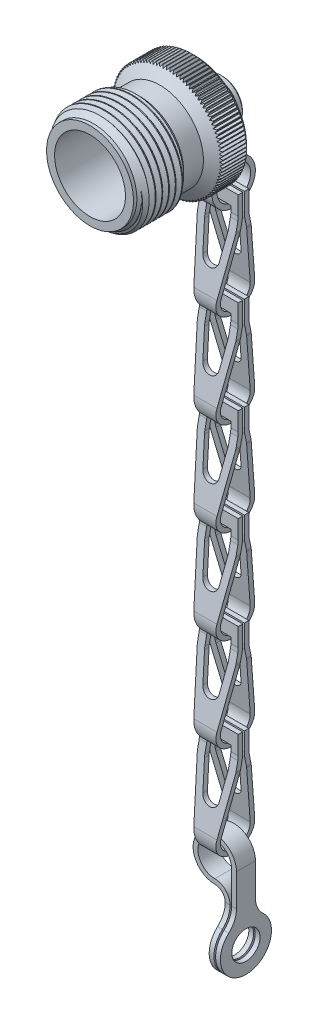
SolidWorks part; units mm, degrees
ref_plane "Front Plane" through (0, 0, 0) normal (0, 0, 1) x (1, 0, 0)
ref_plane "Top Plane" through (0, 0, 0) normal (0, 1, 0) x (1, 0, 0)
ref_plane "Right Plane" through (0, 0, 0) normal (1, 0, 0) x (0, 0, -1)
sketch "Sketch1" plane through (0, 0, 0) normal (1, 0, 0) x (0, 0, -1)
  line L0 (16.6624, 8.7249) -> (16.6624, -8.7249) construction
  line L2 (16.6624, 0) -> (16.6624, -114.3) construction
  line L4 (0, 7.9375) -> (0, -7.9375) construction
  line L5 (0, 7.9375) -> (1.0583, 7.9375) construction
  line L13 (0, 0) -> (16.6624, 0) construction
  circle A0 centre (16.6624, -114.3) radius 2.1082 construction
  point P14 (16.6624, -57.15)
  dimension "D" = 4.2164
  dimension "A Thread" = 15.875
  dimension "A Pitch" = 1.0583
  dimension "B" = 16.6624
  dimension "C" = 17.4498
  dimension "E" = 114.3
sketch "Sketch2" plane through (0, 0, 0) normal (0, 0, 1) x (1, 0, 0)
  circle A1 centre (0, 0) radius 8.7249 construction
  point P1 (0, 8.7249)
sketch "Sketch3" plane through (0, 0, 0) normal (1, 0, 0) x (0, 0, -1)
  line L0 (16.6624, 0) -> (0, 0) construction
  line L1 (0.5292, 6.8792) -> (0, 6.8792)
  line L2 (16.6624, 0) -> (16.6624, 2.1082) construction
  line L3 (0.5292, 6.8792) -> (0.5292, 7.9375) construction
  line L4 (0.5292, 7.9375) -> (1.5875, 7.9375) construction
  line L5 (1.5875, 7.9375) -> (0.5292, 6.8792)
  line L6 (1.5875, 7.9375) -> (6.8792, 7.9375)
  line L7 (12.3114, 8.7249) -> (16.0274, 8.7249)
  line L8 (16.6624, 8.0899) -> (16.6624, 4.8514)
  line L9 (17.2974, 2.1082) -> (11.0617, 2.1082)
  line L10 (11.0617, 2.1082) -> (11.0617, 5.6092)
  line L11 (6.8792, 7.9375) -> (7.9375, 6.8792)
  line L12 (7.9375, 6.8792) -> (11.0617, 6.8792)
  line L13 (11.0617, 6.8792) -> (11.0617, 7.4752) construction
  line L14 (7.9375, 6.8792) -> (7.9375, 7.9375) construction
  line L15 (16.0274, 8.7249) -> (16.6624, 8.0899)
  line L16 (7.9375, 7.9375) -> (6.8792, 7.9375) construction
  line L17 (16.6624, 8.7249) -> (16.6624, -8.7249) construction
  line L18 (16.6624, 4.8514) -> (17.2974, 4.2164)
  line L19 (17.2974, 4.2164) -> (17.2974, 2.1082)
  line L20 (16.6624, 8.7249) -> (16.0274, 8.7249) construction
  line L21 (16.6624, 8.7249) -> (16.6624, 8.0899) construction
  line L22 (11.0617, 7.4752) -> (12.3114, 8.7249) construction
  line L23 (12.3114, 8.7249) -> (11.0617, 8.7249) construction
  line L24 (11.0617, 8.7249) -> (11.0617, 7.4752) construction
  line L25 (16.6624, 4.8514) -> (16.6624, 4.2164) construction
  line L26 (16.6624, 4.2164) -> (16.6624, 2.1082) construction
  line L27 (16.6624, 4.2164) -> (17.2974, 4.2164) construction
  line L28 (0, 7.9375) -> (0, -7.9375) construction
  line L29 (0, 6.8792) -> (0, 5.6092)
  line L30 (0, 5.6092) -> (11.0617, 5.6092)
  line L31 (0, 7.9375) -> (1.0583, 7.9375) construction
  line L32 (11.0617, 6.8792) -> (12.3114, 8.7249)
  dimension "D2" = 1.2497
  dimension "D3" = 0.635
  dimension "D4" = 4.2164
  dimension "D5" = 0.635
  dimension "D1" = 5.2917
  dimension "D0" = 7.9375
  dimension "D6" = 5.6007
  dimension "D7" = 1.27
  dimension "D8" = 3.1242
revolve "Revolve1" add sketch "Sketch3" angle 360 about L0
sketch "Sketch4" plane through (0, 0, 0) normal (0, 0, 1) x (1, 0, 0)
  circle A0 centre (0, 0) radius 7.9375
  point P3 (0, 7.9375)
sketch "Sketch13" plane through (0, 0, 0) normal (1, 0, 0) x (0, 0, -1)
  line L0 (16.6624, 2.1082) -> (17.2974, 1.0541)
  line L1 (17.2974, -4.2164) -> (17.2974, 4.2164) construction
  line L2 (16.6624, 0) -> (16.6624, 2.1082) construction
  line L3 (16.6624, 2.1082) -> (17.2974, 2.1082)
  line L4 (17.2974, 2.1082) -> (17.2974, 1.0541)
  point P6 (16.6624, 1.0541)
revolve "Revolve4" add sketch "Sketch13" angle 360 about L13
sketch "Sketch8" plane through (0, 0, 0) normal (1, 0, 0) x (0, 0, -1)
  line L0 (20.9804, 0) -> (0, 0) construction
  line L1 (20.0914, 2.1082) -> (20.0914, 3.3782)
  line L2 (11.0617, 2.1082) -> (20.0914, 2.1082) construction
  line L3 (11.0617, 2.1082) -> (11.0617, 0) construction
  line L4 (11.0617, 0) -> (20.9804, 0) construction
  line L5 (20.9804, 3.1242) -> (20.9804, 0)
  line L6 (20.0914, 3.3782) -> (20.7264, 3.3782)
  line L7 (20.7264, 3.3782) -> (20.9804, 3.1242)
  line L8 (20.9804, 3.1242) -> (20.9804, 3.3782) construction
  line L9 (20.9804, 3.3782) -> (20.7264, 3.3782) construction
  line L10 (17.2974, 2.1082) -> (17.2974, 1.0541)
  line L11 (17.2974, 1.0541) -> (11.0617, 1.0541)
  line L12 (11.0617, 1.0541) -> (11.0617, 0)
  line L13 (11.0617, 0) -> (20.9804, 0)
  line L14 (17.2974, 2.1082) -> (20.0914, 2.1082)
  dimension "D1" = 4.318
  dimension "D2" = 1.27
  dimension "D3" = 0.889
  dimension "D4" = 0.254
revolve "Revolve3" add sketch "Sketch8" angle 360 about L0
sketch "Sketch14" plane through (0, 0, -11.0617) normal (0, 0, 1) x (1, 0, 0)
  circle A2 centre (0, 0) radius 0.8001
  circle A3 centre (0, 0) radius 0.8001
  dimension "D1" = 0.254
extrude "Cut-Extrude4" cut sketch "Sketch14" against normal offset from surface (4.6482 mm away) 1.5875 up to face at (-4.2164, 0, -17.2974)
sketch "Sketch15" plane through (0, 0, -15.7099) normal (0, 0, 1) x (1, 0, 0)
  circle A0 centre (0, 0) radius 0.1984
  dimension "D1" = 0.3969
extrude "Boss-Extrude3" add sketch "Sketch15" along normal blind 0.635
sketch "Sketch9" plane through (0, 0, 0) normal (1, 0, 0) x (0, 0, -1)
  line L0 (17.2974, 0) -> (20.0914, 0) construction
  line L1 (20.0914, 2.1082) -> (20.0914, -2.1082) construction
  line L5 (18.6944, 0) -> (18.6944, 4.064) construction
  line L6 (18.5674, 4.064) -> (18.8214, 4.064) construction
  line L7 (18.5674, 4.064) -> (18.5674, -10.795)
  line L8 (18.5674, 4.064) -> (17.8054, 4.064)
  line L9 (17.8054, 4.064) -> (17.8054, -10.795)
  line L10 (19.5834, -5.715) -> (19.5834, 4.064)
  line L11 (19.5834, 4.064) -> (18.8214, 4.064)
  line L12 (18.8214, 4.064) -> (18.8214, -5.715)
  line L14 (17.2974, -2.1082) -> (17.2974, 2.1082) construction
  arc A0 (17.8054, -10.795) -> (21.2344, -7.366) centre (21.2344, -10.795) ccw
  arc A1 (21.2344, -7.366) -> (19.5834, -5.715) centre (21.2344, -5.715) cw
  arc A2 (18.8214, -5.715) -> (21.2344, -8.128) centre (21.2344, -5.715) ccw
  arc A3 (21.2344, -8.128) -> (18.5674, -10.795) centre (21.2344, -10.795) cw
  dimension "D5" = 3.429
  dimension "D1" = 0.762
  dimension "D2" = 0.254
  dimension "D3" = 18.288
  dimension "D4" = 4.064
extrude "Boss-Extrude1" add sketch "Sketch9" along normal mid plane 8.128 separate body
sketch "Sketch10" plane through (0, 0, -17.8054) normal (0, 0, 1) x (1, 0, 0)
  line L0 (1.4986, -14.224) -> (-1.4986, -14.224)
  line L1 (0, 0) -> (0, -14.224) construction
  line L2 (-4.064, -14.224) -> (4.064, -14.224) construction
  line L3 (-1.4986, -14.224) -> (-1.4986, -5.715)
  line L4 (1.4986, -14.224) -> (1.4986, -5.715)
  line L5 (4.064, -5.715) -> (-4.064, -5.715) construction
  arc A1 (2.7063, -2.9977) -> (-2.7063, -2.9977) centre (0, 0) ccw
  circle A3 centre (0, 0) radius 2.2352
  arc A4 (-2.7063, -2.9977) -> (-1.4986, -5.715) centre (-5.1594, -5.715) cw
  arc A5 (2.7063, -2.9977) -> (1.4986, -5.715) centre (5.1594, -5.715) ccw
  circle A6 centre (0, 0) radius 2.2352
  dimension "D2" = 8.0772
  dimension "D3" = 2.9972
  dimension "D1" = 0.127
extrude "Cut-Extrude2" cut sketch "Sketch10" against normal blind 8.128 flip side to cut
sketch "Sketch11" plane through (0, 0, 0) normal (1, 0, 0) x (0, 0, -1)
  line L0 (21.2344, -11.303) -> (21.2344, -28.956) construction
  line L1 (21.3614, -11.303) -> (21.1074, -11.303) construction
  line L2 (21.1074, -11.303) -> (20.3962, -11.303)
  line L3 (20.3962, -11.303) -> (20.3962, -14.224)
  line L4 (20.3348, -14.8456) -> (18.2454, -25.3113)
  line L5 (21.1074, -11.303) -> (21.1074, -14.224)
  line L6 (21.0322, -14.9848) -> (18.9428, -25.4505)
  line L7 (21.4366, -14.9848) -> (23.526, -25.4505)
  line L8 (22.134, -14.8456) -> (24.2234, -25.3113)
  line L9 (21.3614, -11.303) -> (21.3614, -14.224)
  line L10 (22.0726, -11.303) -> (22.0726, -14.224)
  line L11 (21.3614, -11.303) -> (22.0726, -11.303)
  line L12 (21.1074, -14.224) -> (21.3614, -14.224) construction
  arc A0 (18.2454, -25.3113) -> (24.2234, -25.3113) centre (21.2344, -25.908) ccw
  arc A1 (18.9428, -25.4505) -> (23.526, -25.4505) centre (21.2344, -25.908) ccw
  arc A2 (20.3962, -14.224) -> (20.3348, -14.8456) centre (17.2212, -14.224) cw
  arc A3 (21.1074, -14.224) -> (21.0322, -14.9848) centre (17.2212, -14.224) cw
  arc A4 (21.3614, -14.224) -> (21.4366, -14.9848) centre (25.2476, -14.224) ccw
  arc A5 (22.0726, -14.224) -> (22.134, -14.8456) centre (25.2476, -14.224) ccw
  arc A6 (18.5674, -10.795) -> (21.2344, -8.128) centre (21.2344, -10.795) ccw construction
  arc A7 (17.8054, -10.795) -> (21.2344, -7.366) centre (21.2344, -10.795) ccw construction
  point P6 (21.2344, -13.462)
  point P11 (21.2344, -14.224)
  point P27 (21.2344, -28.2448)
  dimension "D4" = 3.048
  dimension "D6" = 3.175
  dimension "D1" = 0.7112
  dimension "D2" = 17.653
  dimension "D3" = 2.159
  dimension "D5" = 0.254
  dimension "D7" = 14.7828
extrude "Boss-Extrude2" add sketch "Sketch11" along normal mid plane 6.096 separate body
sketch "Sketch12" plane through (0, 0, -21.1074) normal (0, 0, -1) x (-1, 0, 0)
  line L0 (0, -13.335) -> (0, -21.971) construction
  line L1 (-1.8796, -13.335) -> (1.8796, -13.335)
  line L2 (-1.8796, -13.335) -> (-1.8796, -16.294)
  line L3 (1.8503, -16.724) -> (1.2866, -20.8483)
  line L4 (1.8796, -13.335) -> (1.8796, -16.294)
  line L5 (-1.8503, -16.724) -> (-1.2866, -20.8483)
  line L6 (-3.048, -16.294) -> (-3.048, -28.956)
  line L7 (-3.048, -28.956) -> (-1.3335, -28.956)
  line L8 (-1.3335, -28.956) -> (-3.0319, -16.5314)
  line L9 (1.3335, -28.956) -> (3.0319, -16.5314)
  line L10 (3.048, -28.956) -> (1.3335, -28.956)
  line L11 (3.048, -16.294) -> (3.048, -28.956)
  arc A0 (-1.2866, -20.8483) -> (1.2866, -20.8483) centre (0, -20.6725) ccw
  arc A1 (-1.8796, -16.294) -> (-1.8503, -16.724) centre (1.2954, -16.294) ccw
  arc A2 (1.8796, -16.294) -> (1.8503, -16.724) centre (-1.2954, -16.294) cw
  arc A3 (-3.0319, -16.5314) -> (-3.048, -16.294) centre (-1.2954, -16.294) cw
  arc A4 (3.0319, -16.5314) -> (3.048, -16.294) centre (1.2954, -16.294) ccw
  point P12 (-1.8796, -16.51)
  dimension "D4" = 2.667
  dimension "D6" = 3.175
  dimension "D1" = 2.032
  dimension "D2" = 3.7592
  dimension "D3" = 8.636
  dimension "D5" = 3.175
extrude "Cut-Extrude3" cut sketch "Sketch12" against normal up to next and the other way up to next
pattern_linear "LPattern1" count 6 spacing 14.7828 along (0, -1, 0) of bodies 162
ref_plane "Plane1" through (0, -57.15, 0) normal (0, 1, 0) x (-1, 0, 0)
mirror "Mirror1" about plane through (0, -57.15, 0) normal (0, 1, 0) of bodies 160
move or copy body "Body-Move/Copy1" bodies to move or copy 168 copy no rotation origin (0, 0, -21.2344) rotation axis (0, 1, 0) rotation angle 90
curve "Helix/Spiral1" pitch 1.0583 height 8.9959 turns 8.5
sketch "Sketch5" plane through (0, 0, 0) normal (1, 0, 0) x (0, 0, -1)
  line L0 (-0.463, 7.1355) -> (0.0661, 8.0521) construction
  line L1 (0.0661, 8.0521) -> (-0.9922, 8.0521) construction
  line L2 (-0.9922, 8.0521) -> (-0.463, 7.1355) construction
  line L3 (0, 7.9375) -> (-0.926, 7.9375) construction
  line L4 (-0.5292, 7.2501) -> (-0.3969, 7.2501) construction
  line L5 (-0.463, 7.1355) -> (-0.463, 7.2501) construction
  line L6 (-0.463, 7.9375) -> (-0.463, 8.0521) construction
  line L7 (-0.3969, 7.2501) -> (0.0331, 7.9948)
  line L8 (0.0331, 7.9948) -> (-0.9591, 7.9948)
  line L9 (-0.9591, 7.9948) -> (-0.5292, 7.2501)
  line L10 (-0.5292, 7.2501) -> (-0.3969, 7.2501)
  point P14 (-0.463, 7.9948)
  dimension "D1" = 1.0583
  dimension "D2" = 0.1323
sweep "Cut-Sweep1" cut profiles "Sketch5" path "Helix/Spiral1"
ref_plane "Plane2" through (0, 0, -11.0617) normal (0, 0, 1) x (1, 0, 0)
sketch "Sketch6" plane through (0, 0, -11.0617) normal (0, 0, 1) x (1, 0, 0)
  line L0 (-0.2284, 8.7219) -> (0, 8.4074)
  line L1 (0, 8.4074) -> (0.2284, 8.7219)
  line L2 (0, 8.4074) -> (0, 8.7249) construction
  line L3 (-0.2284, 8.7219) -> (0, 0) construction
  line L4 (0, 0) -> (0.2284, 8.7219) construction
  arc A1 (0.2284, 8.7219) -> (-0.2284, 8.7219) centre (0, 0) ccw
  circle A2 centre (0, 0) radius 8.7249 construction
  circle A3 centre (0, 0) radius 8.7249 construction
  dimension "D1" = 3
  dimension "D2" = 0.3175
extrude "Cut-Extrude1" cut sketch "Sketch6" against normal up to surface (5.6007 mm away) up to face at (-8.0899, 0, -16.6624)
pattern_circular "CirPattern1" count 100 over 360 about axis through (0, 0, 0) along (0, 0, 1) of "Cut-Extrude1"
equation "\"D4@Helix/Spiral1\" = \"A Pitch@Sketch1\""
equation "\"D3@Helix/Spiral1\" = \"D0@Sketch3\" + \"D4@Helix/Spiral1\""
equation "\"D1@Sketch5\" = \"D4@Helix/Spiral1\""
equation "\"D2@Sketch5\" = \"D1@Sketch5\" / 8"
equation "\"D4@Sketch3\" = \"D@Sketch1\""
equation "\"D3@LPattern1\" = \"D7@Sketch11\""
equation "\"D8@Sketch3\"=\"B@Sketch1\"*.1875"
equation "\"D2@Sketch3\"=\"D8@Sketch3\"/2.5"
equation "\"D1@Sketch3\"=0.2500in-\"A Pitch@Sketch1\""
